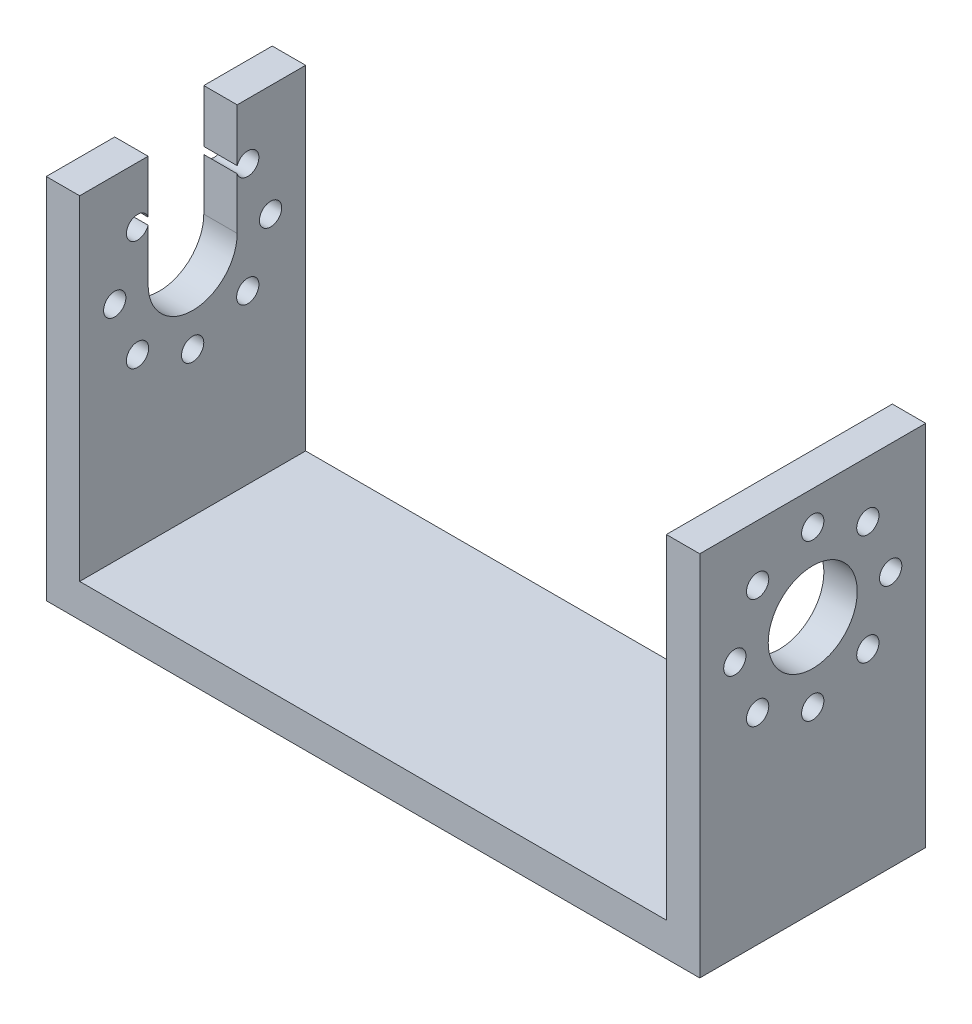
SolidWorks part; units mm, degrees
ref_plane "Front Plane" through (0, 0, 0) normal (0, 0, 1) x (1, 0, 0)
ref_plane "Top Plane" through (0, 0, 0) normal (0, 1, 0) x (1, 0, 0)
ref_plane "Right Plane" through (0, 0, 0) normal (1, 0, 0) x (0, 0, -1)
sketch "Sketch1" plane through (0, 0, 0) normal (0, 1, 0) x (1, 0, 0)
  line L1 (0, 0) -> (58.7, 0)
  line L2 (0, 0) -> (0, 20.3)
  line L3 (0, 20.3) -> (58.7, 20.3)
  line L4 (58.7, 0) -> (58.7, 20.3)
  dimension "D1" = 58.7
  dimension "D2" = 20.3
extrude "YawMount" add sketch "Sketch1" along normal blind 3
sketch "Sketch2" plane through (0, 3, 0) normal (0, 1, 0) x (1, 0, 0)
  line L0 (0, 0) -> (58.7, 0) construction
  line L1 (0, 20.3) -> (3, 20.3)
  line L2 (0, 20.3) -> (0, 0)
  line L3 (0, 0) -> (3, 0)
  line L4 (3, 20.3) -> (3, 0)
  line L6 (58.7, 20.3) -> (55.7, 20.3)
  line L7 (58.7, 20.3) -> (58.7, 0)
  line L8 (58.7, 0) -> (55.7, 0)
  line L9 (55.7, 20.3) -> (55.7, 0)
  dimension "D1" = 3
  dimension "D2" = 3
extrude "BodyConnectors" add sketch "Sketch2" along normal blind 30
sketch "Sketch3" plane through (58.7, 0, 0) normal (1, 0, 0) x (0, 0, -1)
  line L1 (0, 33) -> (20.3, 33) construction
  circle A9 centre (5.2003, 27.9497) radius 1
  circle A10 centre (10.15, 30) radius 1
  circle A11 centre (15.0997, 27.9497) radius 1
  circle A12 centre (17.15, 23) radius 1
  circle A13 centre (15.0997, 18.0503) radius 1
  circle A14 centre (10.15, 16) radius 1
  circle A15 centre (5.2003, 18.0503) radius 1
  circle A16 centre (3.15, 23) radius 1
  point P4 (10.15, 33)
  point P23 (10.15, 23)
  dimension "D1" = 2
  dimension "D2" = 20
  dimension "D3" = 7
extrude "Axle-Mounts" cut sketch "Sketch3" against normal up to surface (58.7 mm away) up to face at (0, 16.5, -10.15)
sketch "Sketch4" plane through (55.7, 0, 0) normal (-1, 0, 0) x (0, 0, 1)
  line L0 (0, 33) -> (-20.3, 33) construction
  circle A0 centre (-10.15, 23) radius 4
  circle A3 centre (-17.15, 23) radius 1 construction
  point P7 (-10.15, 33)
  dimension "D1" = 8
  dimension "D2" = 7
extrude "Axle-Counterbore" cut sketch "Sketch4" against normal up to surface and the other way up to surface up to face at (58.7, 30, -11.15) other way up to face at (0, 30, -11.15)
sketch "Sketch5" plane through (0, 33, 0) normal (0, 1, 0) x (1, 0, 0)
  line L0 (3, 0) -> (3, 20.3) construction
  line L1 (3, 14.15) -> (0, 14.15)
  line L2 (3, 14.15) -> (3, 6.15)
  line L3 (3, 6.15) -> (0, 6.15)
  line L4 (0, 14.15) -> (0, 6.15)
  line L5 (0, 20.3) -> (0, 0) construction
  point P8 (0, 10.15)
  point P9 (0, 10.15)
  dimension "D1" = 8
extrude "MotorAxleSlideGap" cut sketch "Sketch5" against normal blind 10
equation "\"srv_w\"= 40.43mm'width of Sain Smart SR319"
equation "\"D1@Sketch1\"=51.8mm + \"mnt_thick\"*2.3"
equation "\"srv_h\"= 40.61mm'height of Sain Smart SR319"
equation "\"srv_d\"= 20.3mm'depth of Sain Smart SR319"
equation "\"D2@Sketch1\"=\"srv_d\""
equation "\"mnt_thick\"= 3mm'thickness of bracket"
equation "\"D1@YawMount\" = \"mnt_thick\""
equation "\"D2@Sketch2\"=\"mnt_thick\""
equation "\"D1@Sketch2\"=\"mnt_thick\""
